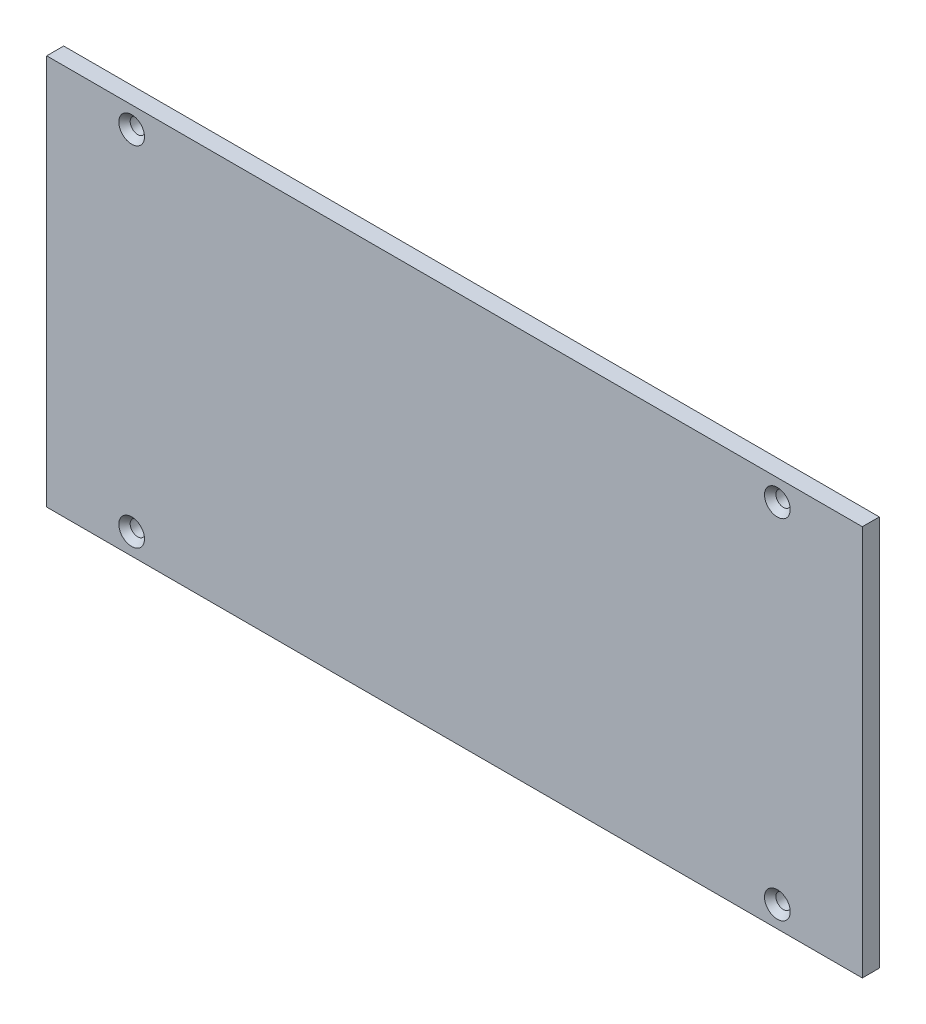
SolidWorks part; units mm, degrees
material "6061-T4 (SS)"
ref_plane "Front Plane" through (0, 0, 0) normal (0, 0, 1) x (1, 0, 0)
ref_plane "Top Plane" through (0, 0, 0) normal (0, 1, 0) x (1, 0, 0)
ref_plane "Right Plane" through (0, 0, 0) normal (1, 0, 0) x (0, 0, -1)
sketch "Sketch1" plane through (0, 0, 0) normal (0, 0, 1) x (1, 0, 0)
  line L1 (0, 0) -> (96, 0)
  line L2 (0, 0) -> (0, 46)
  line L3 (0, 46) -> (96, 46)
  line L4 (96, 0) -> (96, 46)
  dimension "D1" = 46
  dimension "D2" = 96
extrude "Boss-Extrude1" add sketch "Sketch1" along normal blind 2
sketch "Sketch2" plane through (0, 0, 2) normal (0, 0, 1) x (1, 0, 0)
  circle A0 centre (75.2, 23.05) radius 13.1445
  circle A1 centre (75.2, 23.05) radius 13.1445 construction
extrude "Cut-Extrude1" [suppressed] cut sketch "Sketch2" against normal through all
hole_wizard "CSK for #0 Flat Head Machine Screw1" positions "Sketch6" profile "Sketch7" countersink size "#0" standard "ANSI Inch" end condition through all
sketch "Sketch6" plane through (0, 0, 2) normal (0, 0, 1) x (1, 0, 0)
  line L0 (0, 46) -> (0, 0) construction
  line L1 (10, 43.5) -> (10, 2.5) construction
  line L2 (10, 2.5) -> (86, 2.5) construction
  line L3 (86, 2.5) -> (86, 43.5) construction
  line L4 (86, 43.5) -> (10, 43.5) construction
  line L6 (96, 0) -> (96, 46) construction
  line L8 (96, 46) -> (0, 46) construction
  line L9 (0, 0) -> (96, 0) construction
  point P0 (10, 43.5)
  point P2 (10, 2.5)
  point P4 (86, 2.5)
  point P6 (86, 43.5)
  dimension "D1" = 10
  dimension "D2" = 10
  dimension "D3" = 2.5
  dimension "D4" = 2.5
sketch "Sketch7" plane through (10, 43.5, 2) normal (1, 0, 0) x (0, -1, 0)
  line L0 (0, 0) -> (0, 2)
  line L1 (0, 2) -> (0.889, 2)
  line L2 (0.889, 2) -> (0.889, 0.7159)
  line L3 (0.889, 0.7159) -> (1.5113, 0)
  line L5 (1.5113, 0) -> (0, 0)
  line L6 (-0.889, 0.7159) -> (-1.5113, 0) construction
  line L11 (0, -6.35) -> (0, 107.95) construction
  dimension "Thru Hole Dia." = 1.778
  dimension "Thru Hole Depth" = 2
  dimension "Near C'Sink Dia." = 3.0226
  dimension "Near C'Sink Angle" = 82
